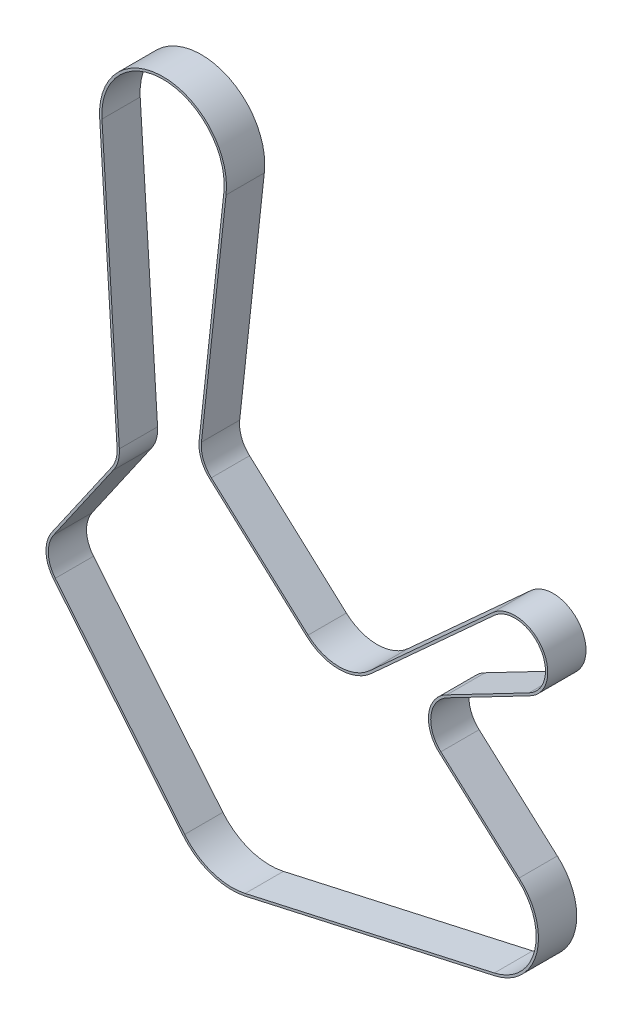
SolidWorks part; units mm, degrees
material "Rubber"
ref_plane "Front Plane" through (0, 0, 0) normal (0, 0, 1) x (1, 0, 0)
ref_plane "Top Plane" through (0, 0, 0) normal (0, 1, 0) x (1, 0, 0)
ref_plane "Right Plane" through (0, 0, 0) normal (1, 0, 0) x (0, 0, -1)
sketch "Sketch2" plane through (0, 0, 0) normal (0, 0, 1) x (1, 0, 0)
  line L0 (0, 0) -> (1, 0) construction
  line L1 (0, 0) -> (0, 1) construction
  line L2 (41.2094, -4.9026) -> (23.6506, -152.4941)
  line L3 (30.5543, -170.958) -> (93.8354, -228.3645)
  line L4 (136.5187, -228.0383) -> (215.3126, -154.3327)
  line L5 (239.4503, -189.3458) -> (185.5497, -215.7224)
  line L6 (180.9815, -251.3354) -> (232.7376, -295.8435)
  line L7 (216.9, -359.139) -> (54.0517, -395.5349)
  line L8 (12.9608, -381.4109) -> (-71.5986, -278.6992)
  line L9 (-72.3897, -252.3909) -> (-32.6103, -197.6772)
  line L10 (-28.5542, -183.5089) -> (-41.3954, -2.9439)
  arc A0 (-41.3954, -2.9439) -> (41.2094, -4.9026) centre (0, 0) cw
  arc A1 (23.6506, -152.4941) -> (30.5543, -170.958) centre (45, -155.0341) ccw
  arc A2 (93.8354, -228.3645) -> (136.5187, -228.0383) centre (115, -205.0341) ccw
  arc A3 (215.3126, -154.3327) -> (239.4503, -189.3458) centre (230, -170.0341) cw
  arc A4 (185.5497, -215.7224) -> (180.9815, -251.3354) centre (195, -235.0341) ccw
  arc A5 (232.7376, -295.8435) -> (216.9, -359.139) centre (208.9388, -323.5178) cw
  arc A6 (54.0517, -395.5349) -> (12.9608, -381.4109) centre (45, -355.0341) cw
  arc A7 (-71.5986, -278.6992) -> (-72.3897, -252.3909) centre (-55, -265.0341) cw
  arc A8 (-32.6103, -197.6772) -> (-28.5542, -183.5089) centre (-50, -185.0341) ccw
sketch "Sketch3" plane through (0, 0, 0) normal (0, 0, 1) x (1, 0, 0)
  line L0 (239.4503, -189.3458) -> (185.5497, -215.7224) construction
  line L1 (216.9, -359.139) -> (54.0517, -395.5349) construction
  line L2 (12.9608, -381.4109) -> (-71.5986, -278.6992) construction
  line L3 (41.2094, -4.9026) -> (25.1233, -152.8732)
  line L4 (31.5663, -169.8425) -> (94.8474, -227.249)
  line L5 (135.1826, -227.2217) -> (215.3126, -154.3327)
  line L6 (239.4503, -189.3458) -> (185.7656, -217.2994)
  line L7 (181.633, -249.904) -> (232.7376, -295.8435)
  line L8 (216.9, -359.139) -> (54.0517, -395.5349)
  line L9 (12.9608, -381.4109) -> (-71.5986, -278.6992)
  line L10 (-72.3897, -252.3909) -> (-33.5719, -196.4295)
  line L11 (-41.3954, -2.9439) -> (-30.0458, -183.7817)
  line L12 (39.7586, -4.3222) -> (23.6506, -152.4941)
  line L13 (-39.9143, -2.5051) -> (-28.5542, -183.5089)
  line L14 (-32.6103, -197.6772) -> (-71.4281, -253.6386)
  line L15 (-70.4356, -277.7417) -> (14.1239, -380.4534)
  line L16 (216.5714, -357.6688) -> (53.7232, -394.0646)
  line L17 (180.9815, -251.3354) -> (232.0318, -297.226)
  line L18 (239.2344, -187.7687) -> (185.5497, -215.7224)
  line L19 (216.5456, -155.2431) -> (136.5187, -228.0383)
  line L20 (93.8354, -228.3645) -> (30.5543, -170.958)
  arc A0 (41.2094, -4.9026) -> (-41.3954, -2.9439) centre (0, 0) ccw
  arc A1 (41.2094, -4.9026) -> (-41.3954, -2.9439) centre (0, 0) ccw construction
  arc A2 (23.6506, -152.4941) -> (30.5543, -170.958) centre (45, -155.0341) ccw
  arc A3 (23.6506, -152.4941) -> (30.5543, -170.958) centre (45, -155.0341) ccw construction
  arc A4 (215.3126, -154.3327) -> (239.4503, -189.3458) centre (230, -170.0341) cw
  arc A5 (232.7376, -295.8435) -> (216.9, -359.139) centre (208.9388, -323.5178) cw
  arc A6 (54.0517, -395.5349) -> (12.9608, -381.4109) centre (45, -355.0341) cw
  arc A7 (-72.3897, -252.3909) -> (-71.5986, -278.6992) centre (-55, -265.0341) ccw
  arc A8 (-72.3897, -252.3909) -> (-71.5986, -278.6992) centre (-55, -265.0341) ccw construction
  arc A9 (-28.5542, -183.5089) -> (-32.6103, -197.6772) centre (-50, -185.0341) cw
  arc A10 (-32.6103, -197.6772) -> (-28.5542, -183.5089) centre (-50, -185.0341) ccw construction
  arc A11 (185.5497, -215.7224) -> (180.9815, -251.3354) centre (195, -235.0341) ccw
  arc A12 (185.5497, -215.7224) -> (180.9815, -251.3354) centre (195, -235.0341) ccw construction
  arc A13 (93.8354, -228.3645) -> (136.5187, -228.0383) centre (115, -205.0341) ccw
  arc A14 (93.8354, -228.3645) -> (136.5187, -228.0383) centre (115, -205.0341) ccw construction
  arc A15 (39.7586, -4.3222) -> (-39.9143, -2.5051) centre (0, 0) ccw
  arc A16 (239.2344, -187.7687) -> (216.5456, -155.2431) centre (230, -170.0341) ccw
  arc A17 (216.5714, -357.6688) -> (232.0318, -297.226) centre (208.9388, -323.5178) ccw
  arc A18 (53.7232, -394.0646) -> (14.1239, -380.4534) centre (45, -355.0341) cw
  arc A19 (-71.4281, -253.6386) -> (-70.4356, -277.7417) centre (-55, -265.0341) ccw
  arc A20 (135.1826, -227.2217) -> (94.8474, -227.249) centre (115, -205.0341) cw
  arc A21 (25.1233, -152.8732) -> (31.5663, -169.8425) centre (45, -155.0341) ccw
  arc A22 (-30.0458, -183.7817) -> (-33.5719, -196.4295) centre (-50, -185.0341) cw
  arc A23 (185.7656, -217.2994) -> (181.633, -249.904) centre (195, -235.0341) ccw
  dimension "D1" = 1.5
extrude "Boss-Extrude1" add sketch "Sketch3" along normal blind 12.5 and the other way blind 12.5
